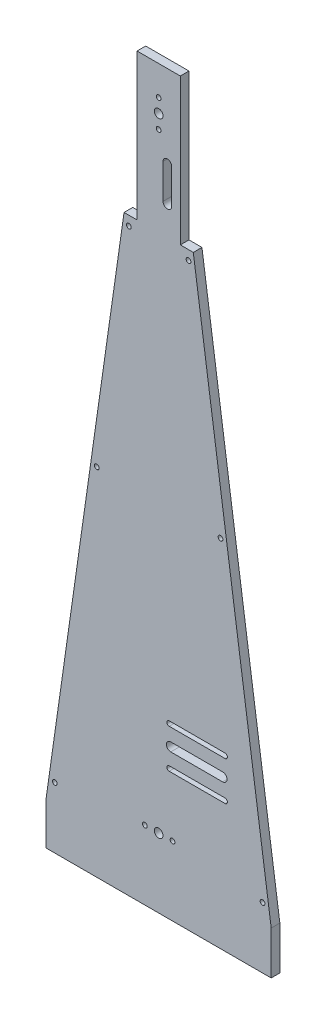
SolidWorks part; units mm, degrees
ref_plane "Ebene vorne" through (0, 0, 0) normal (0, 0, 1) x (1, 0, 0)
ref_plane "Ebene oben" through (0, 0, 0) normal (0, 1, 0) x (1, 0, 0)
ref_plane "Ebene rechts" through (0, 0, 0) normal (1, 0, 0) x (0, 0, -1)
sketch "Skizze1" plane through (0, 0, 0) normal (0, 0, 1) x (1, 0, 0)
  line L0 (-40, 681) -> (-130, 50)
  line L1 (-263.5092, 681) -> (296.6943, 681) construction
  line L2 (0, 800) -> (0, 0)
  line L3 (-25, 800) -> (-25, 681)
  line L4 (-40, 681) -> (-25, 681)
  line L5 (0, 800) -> (0, 850)
  line L7 (-130, 0) -> (-130, 50)
  line L10 (40, 681) -> (25, 681)
  line L12 (-130, 0) -> (0, 0)
  line L13 (-32.9292, 681) -> (-123.0701, 49.0116) construction
  line L14 (-33.0701, 680.0116) -> (-123.0701, 49.0116) construction
  line L15 (-25, 800) -> (-25, 850)
  line L16 (-25, 850) -> (0, 850)
  point P2 (0, 800)
  point P4 (0, 681)
  point P8 (-40, 681)
  point P12 (-119.9898, 70.6083)
  point P18 (-71.4708, 410.7801)
  point P21 (-34.4874, 670.075)
  point P23 (0, 816)
  point P24 (0, 784)
  dimension "D2" = 25
  dimension "D5" = 50
  dimension "D6" = 130
  dimension "D1" = 800
  dimension "D3" = 119
  dimension "D4" = 40
  dimension "D8" = 50
  dimension "D9" = 16
  dimension "D10" = 16
  dimension "D7" = 7
extrude "Aufsatz-Linear austragen1" add sketch "Skizze1" along normal blind 10 contours L2 L12 L7 L0 L4 L3 L15 L16 L5
mirror "Spiegeln1" about plane through (0, 800, 10) normal (1, 0, 0) of "Aufsatz-Linear austragen1"
hole_wizard "Ø5.5 (5.5) Durchmesser Bohrung1" positions "Skizze2" profile "Skizze3" hole size "Ø5.5" standard "ISO" end condition through all
sketch "Skizze2" plane through (0, 0, 10) normal (0, 0, 1) x (1, 0, 0)
  point P0 (-34.4874, 670.075)
  point P3 (-71.4708, 410.7801)
  point P6 (-119.9898, 70.6083)
  point P9 (0, 816)
  point P12 (0, 784)
sketch "Skizze3" plane through (-34.4874, 670.075, 10) normal (1, 0, 0) x (0, -1, 0)
  line L0 (0, 0) -> (0, 10)
  line L1 (0, 10) -> (2.75, 10)
  line L2 (2.75, 10) -> (2.75, 0)
  line L5 (2.75, 0) -> (0, 0)
  line L11 (0, -6.35) -> (0, 107.95) construction
  dimension "Bohrerdurchmesser" = 5.5
  dimension "Bohrungstiefe" = 10
hole_wizard "Ø10.0 (10) Durchmesser Bohrung1" positions "Skizze6" profile "Skizze5" hole size "Ø10.0" standard "ISO" end condition through all
sketch "Skizze6" plane through (0, 0, 10) normal (0, 0, 1) x (1, 0, 0)
  line L0 (0, 800) -> (0, 0) construction
  line L1 (-130, 0) -> (130, 0) construction
  point P0 (0, 800)
  point P3 (0, 80)
  point P15 (0, 0)
  point P16 (0, 0)
  dimension "D1" = 80
sketch "Skizze5" plane through (0, 800, 10) normal (1, 0, 0) x (0, -1, 0)
  line L0 (0, 0) -> (0, 10)
  line L1 (0, 10) -> (5, 10)
  line L2 (5, 10) -> (5, 0)
  line L5 (5, 0) -> (0, 0)
  line L11 (0, -6.35) -> (0, 107.95) construction
  dimension "Bohrerdurchmesser" = 10
  dimension "Bohrungstiefe" = 10
mirror "Spiegeln2" about plane through (0, 0, 0) normal (1, 0, 0) of "Ø5.5 (5.5) Durchmesser Bohrung1"
hole_wizard "Ø5.5 (5.5) Durchmesser Bohrung2" positions "Skizze7" profile "Skizze8" hole size "Ø5.5" standard "ISO" end condition through all
sketch "Skizze7" plane through (0, 0, 10) normal (0, 0, 1) x (1, 0, 0)
  line L1 (0, 80) -> (-104.9668, 80) construction
  line L3 (0, 80) -> (96.42, 80) construction
  circle A0 centre (0, 80) radius 5 construction
  point P0 (-16, 80)
  point P4 (16, 80)
  dimension "D1" = 16
  dimension "D2" = 16
sketch "Skizze8" plane through (-16, 80, 10) normal (1, 0, 0) x (0, -1, 0)
  line L0 (0, 0) -> (0, 10)
  line L1 (0, 10) -> (2.75, 10)
  line L2 (2.75, 10) -> (2.75, 0)
  line L5 (2.75, 0) -> (0, 0)
  line L11 (0, -6.35) -> (0, 107.95) construction
  dimension "Bohrerdurchmesser" = 5.5
  dimension "Bohrungstiefe" = 10
hole_wizard "Ø10.0 (10) Durchmesser Langloch1" positions "Skizze9" profile "Skizze10" size "Ø10.0" standard "ISO" slot yes end condition through all
sketch "Skizze9" plane through (0, 0, 10) normal (0, 0, 1) x (1, 0, 0)
  line L0 (8.9197, 173.191) -> (78.9197, 173.191) construction
  point P0 (43.9197, 173.191)
  point P6 (64.0582, 189.383)
  point P7 (43.9197, 173.191)
  dimension "D1" = 70
sketch "Skizze10" plane through (43.9197, 173.191, 10) normal (1, 0, 0) x (0, -1, 0)
  line L0 (0, 0) -> (0, 10)
  line L1 (0, 10) -> (5, 10)
  line L2 (5, 10) -> (5, 0)
  line L5 (5, 0) -> (0, 0)
  line L11 (0, -6.35) -> (0, 107.95) construction
  dimension "Bohrerdurchmesser" = 10
  dimension "Bohrungstiefe" = 10
hole_wizard "Ø10.0 (10) Durchmesser Langloch3" positions "Skizze11" profile "Skizze12" size "Ø10.0" standard "ISO" slot yes end condition through all
sketch "Skizze11" plane through (0, 0, 10) normal (0, 0, 1) x (1, 0, 0)
  line L0 (10, 759.5208) -> (10, 709.5208) construction
  line L1 (25, 850) -> (25, 681) construction
  point P0 (10, 734.5208)
  point P18 (0, 0)
  point P21 (11.6592, 738.8192)
  point P22 (11.6592, 734.545)
  point P23 (0, 0)
  point P24 (11.8767, 709.5208)
  dimension "D1" = 50
  dimension "D2" = 15
sketch "Skizze12" plane through (10, 734.5208, 10) normal (1, 0, 0) x (0, -1, 0)
  line L0 (0, 0) -> (0, 10)
  line L1 (0, 10) -> (5, 10)
  line L2 (5, 10) -> (5, 0)
  line L5 (5, 0) -> (0, 0)
  line L11 (0, -6.35) -> (0, 107.95) construction
  dimension "Bohrerdurchmesser" = 10
  dimension "Bohrungstiefe" = 10
hole_wizard "Ø5.5 (5.5) Durchmesser Langloch1" positions "Skizze13" profile "Skizze14" size "Ø5.5" standard "ISO" slot yes end condition through all
sketch "Skizze13" plane through (0, 0, 10) normal (0, 0, 1) x (1, 0, 0)
  line L0 (9.3832, 195.691) -> (79.3832, 195.691) construction
  line L1 (44.3832, 195.691) -> (44.3832, 150.691) construction
  arc A0 (13.9197, 178.191) -> (13.9197, 168.191) centre (13.9197, 173.191) ccw construction
  point P0 (44.3832, 195.691)
  point P4 (44.3832, 150.691)
  point P10 (8.9197, 173.191)
  point P15 (44.3832, 195.691)
  point P16 (44.3832, 150.691)
  dimension "D1" = 70
  dimension "D2" = 22.5
  dimension "D3" = 22.5
sketch "Skizze14" plane through (44.3832, 195.691, 10) normal (1, 0, 0) x (0, -1, 0)
  line L0 (0, 0) -> (0, 10)
  line L1 (0, 10) -> (2.75, 10)
  line L2 (2.75, 10) -> (2.75, 0)
  line L5 (2.75, 0) -> (0, 0)
  line L11 (0, -6.35) -> (0, 107.95) construction
  dimension "Bohrerdurchmesser" = 5.5
  dimension "Bohrungstiefe" = 10
